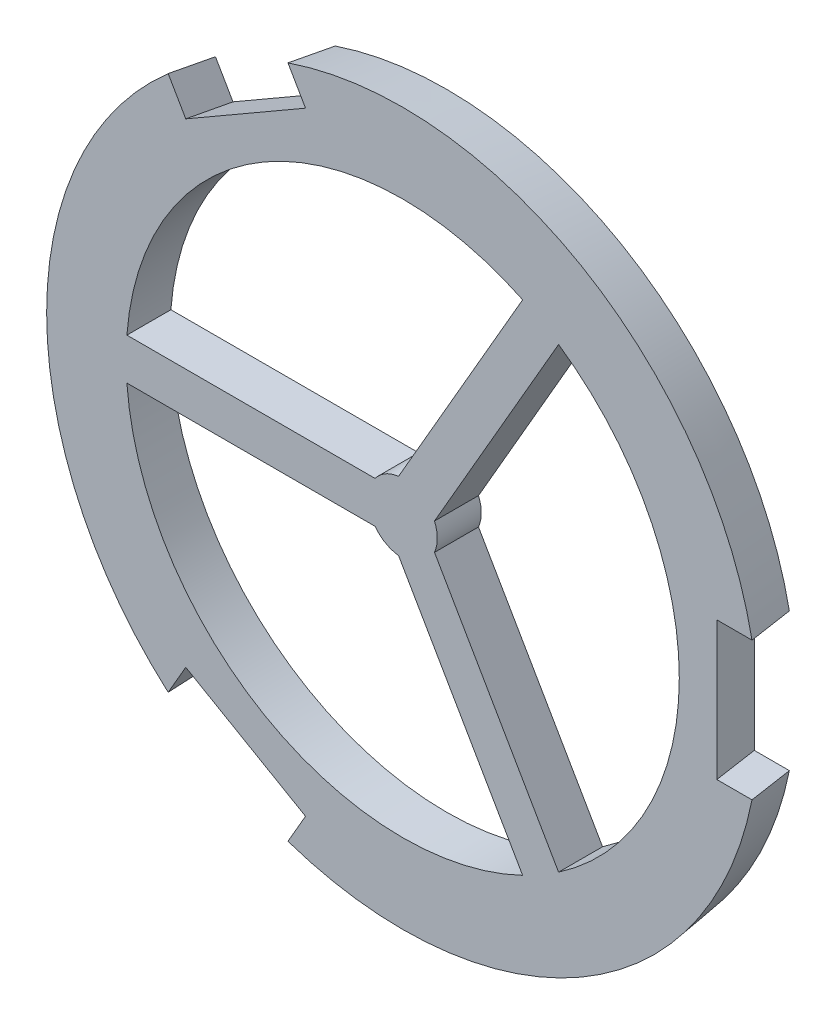
SolidWorks part; units mm, degrees
ref_plane "Front Plane" through (0, 0, 0) normal (0, 0, 1) x (1, 0, 0)
ref_plane "Top Plane" through (0, 0, 0) normal (0, 1, 0) x (1, 0, 0)
ref_plane "Right Plane" through (0, 0, 0) normal (1, 0, 0) x (0, 0, -1)
sketch "Sketch1" plane through (0, 0, 0) normal (0, 1, 0) x (1, 0, 0)
  line L0 (0, 0) -> (0, -208.1822) construction
  line L1 (0, -208.1822) -> (25.7468, -208.1822)
  line L2 (17.3608, -151.4166) -> (37.3725, -286.8769) construction
  line L3 (0, -208.1822) -> (0, -205.0016)
  line L4 (0, -205.0016) -> (25.277, -205.0016)
  line L5 (25.277, -205.0016) -> (25.7468, -208.1822)
revolve "Revolve1" add sketch "Sketch1" angle 360 about L0
sketch "Sketch2" plane through (0, 0, 0) normal (0, 1, 0) x (1, 0, 0)
  line L0 (22.7143, -208.1822) -> (22.2444, -205.0016)
  line L1 (14.393, -151.855) -> (34.7831, -289.8769) construction
  line L2 (-25.7468, -208.1822) -> (25.7468, -208.1822) construction
  line L3 (25.277, -205.0016) -> (-25.277, -205.0016) construction
  line L4 (22.2444, -205.0016) -> (25.277, -205.0016)
  line L5 (25.277, -205.0016) -> (25.7468, -208.1822)
  line L6 (25.7468, -208.1822) -> (22.7143, -208.1822)
  line L7 (22.0941, -203.9844) -> (22.8506, -209.1048)
  line L8 (22.8506, -209.1048) -> (26.7376, -209.1048)
  line L9 (26.7376, -209.1048) -> (25.7468, -203.9844)
  line L10 (25.7468, -203.9844) -> (22.0941, -203.9844)
extrude "Cut-Extrude1" cut sketch "Sketch2" against normal blind 5 and the other way blind 5 contours L10 L7 L8 L9
pattern_circular "CirPattern1" count 3 over 360 about axis through (0, 0, 208.1822) along (0, 0, -1) of "Cut-Extrude1"
sketch "Sketch3" plane through (0, 0, 205.0016) normal (0, 0, -1) x (-1, 0, 0)
  line L0 (-2.299, -0.9821) -> (-11.2709, -16.5217)
  line L1 (-2.299, 0.9821) -> (-11.2709, 16.5217)
  line L2 (2, 1.5) -> (19.9437, 1.5)
  line L8 (2, -1.5) -> (19.9437, -1.5)
  line L15 (0.299, -2.4821) -> (-8.6728, -18.0217)
  line L24 (0.299, 2.4821) -> (-8.6728, 18.0217)
  circle A0 centre (0, 0) radius 20
  arc A1 (-2.299, 0.9821) -> (-2.299, -0.9821) centre (0, 0) ccw
  arc A2 (2, 1.5) -> (0.299, 2.4821) centre (0, 0) ccw
  arc A3 (0.299, -2.4821) -> (2, -1.5) centre (0, 0) ccw
  point P55 (0, 0)
extrude "Cut-Extrude2" cut sketch "Sketch3" against normal up to surface (3.1806 mm away) contours A1 L1 A0 L0 | A2 L2 A0 L24 | A3 L15 A0 L8 region at (11.9082, 0, 205.0016) region at (-5.9541, -10.3128, 205.0016) region at (-5.9541, 10.3128, 205.0016) up to face at (0, 0, 208.1822)
